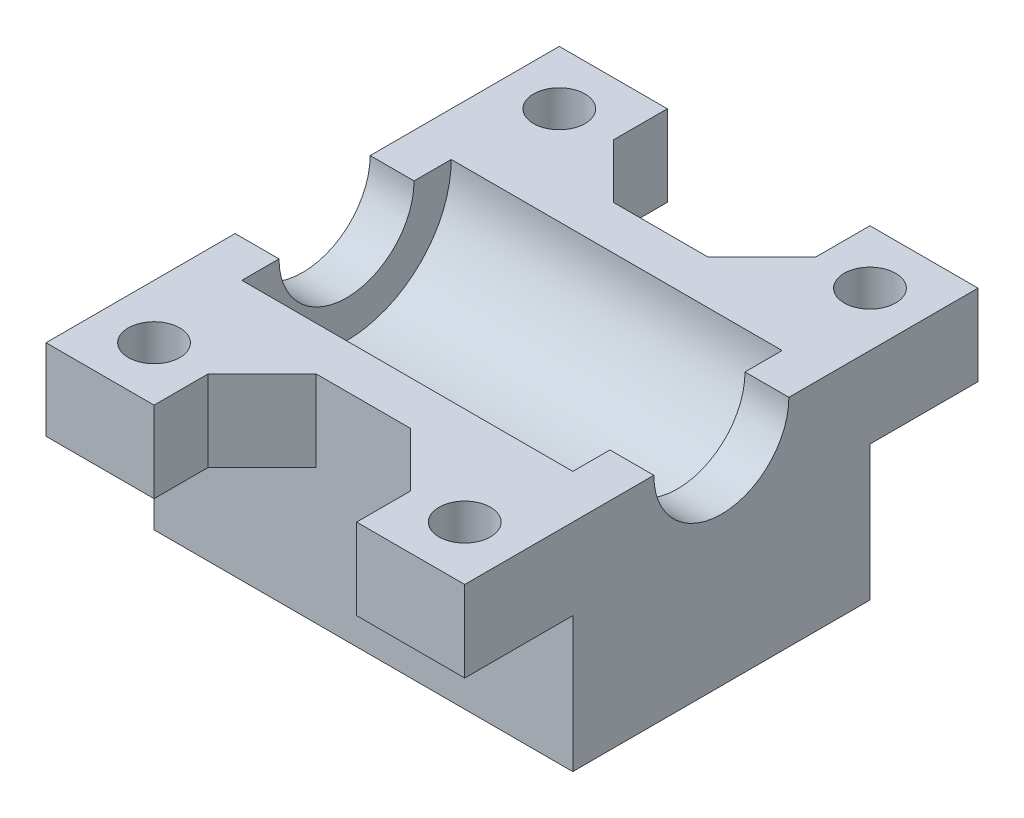
SolidWorks part; units mm, degrees
ref_plane "Front Plane" through (0, 0, 0) normal (0, 0, 1) x (1, 0, 0)
ref_plane "Top Plane" through (0, 0, 0) normal (0, 1, 0) x (1, 0, 0)
ref_plane "Right Plane" through (0, 0, 0) normal (1, 0, 0) x (0, 0, -1)
sketch "Sketch1" plane through (0, 0, 0) normal (0, 1, 0) x (1, 0, 0)
  line L1 (-15.5, 11) -> (15.5, 11)
  line L2 (-15.5, 11) -> (-15.5, -11)
  line L3 (-15.5, -11) -> (15.5, -11)
  line L4 (15.5, 11) -> (15.5, -11)
  line L5 (-15.5, 11) -> (15.5, -11) construction
  line L6 (-15.5, -11) -> (15.5, 11) construction
  point P0 (0, 0)
  dimension "D1" = 31
  dimension "D2" = 22
extrude "Boss-Extrude1" add sketch "Sketch1" along normal blind 11
sketch "Sketch2" plane through (0, 0, 0) normal (0, 1, 0) x (1, 0, 0)
  line L4 (15.5, -11) -> (15.5, 11)
  line L5 (-15.5, -11) -> (15.5, -11)
  line L6 (-15.5, 11) -> (-15.5, -11)
  line L7 (15.5, 11) -> (-15.5, 11)
  line L8 (15.5, -11) -> (15.5, 11)
  line L9 (-15.5, -11) -> (15.5, -11)
  line L10 (-15.5, 11) -> (-15.5, -11)
  line L11 (15.5, 11) -> (-15.5, 11)
  circle A0 centre (0, 0) radius 7.8438
  dimension "D1" = 0
extrude "Boss-Extrude2" add sketch "Sketch2" against normal blind 5
sketch "Sketch3" plane through (0, 11, 0) normal (0, 1, 0) x (1, 0, 0)
  line L1 (12.25, -7.75) -> (-12.25, -7.75)
  line L2 (12.25, -7.75) -> (12.25, 7.75)
  line L3 (12.25, 7.75) -> (-12.25, 7.75)
  line L4 (-12.25, -7.75) -> (-12.25, 7.75)
  line L5 (12.25, -7.75) -> (-12.25, 7.75) construction
  line L6 (12.25, 7.75) -> (-12.25, -7.75) construction
  point P0 (0, 0)
  dimension "D1" = 15.5
  dimension "D2" = 24.5
extrude "Cut-Extrude1" cut sketch "Sketch3" against normal blind 7.75
fillet "Fillet1" radius 7.75 2 edges at (0, 3.25, 7.75) (0, 3.25, -7.75)
sketch "Sketch4" plane through (-12.25, 0, 0) normal (1, 0, 0) x (0, 0, -1)
  line L0 (7.75, 11) -> (-7.75, 11) construction
  circle A0 centre (0, 11) radius 5
  point P4 (0, 0)
  dimension "D1" = 10
extrude "Cut-Extrude2" cut sketch "Sketch4" against normal through all both and the other way through all
sketch "Sketch5" plane through (0, 11, 0) normal (0, 1, 0) x (1, 0, 0)
  line L1 (15.5, -11) -> (7.5, -11)
  line L2 (15.5, -11) -> (15.5, -19)
  line L3 (15.5, -19) -> (7.5, -19)
  line L4 (7.5, -11) -> (7.5, -19)
  circle A0 centre (11.5, -15) radius 1.9058
  dimension "D1" = 8
  dimension "D2" = 8
  dimension "D3" = 4
  dimension "D4" = 4
extrude "Boss-Extrude3" add sketch "Sketch5" against normal blind 6
sketch "Sketch6" plane through (0, 5, 0) normal (0, -1, 0) x (1, 0, 0)
  line L4 (15.5, 11) -> (15.5, 19)
  line L5 (15.5, 19) -> (7.5, 19)
  line L6 (7.5, 19) -> (7.5, 11)
  line L7 (7.5, 11) -> (15.5, 11)
  line L8 (15.5, 11) -> (15.5, 19)
  line L9 (15.5, 19) -> (7.5, 19)
  line L10 (7.5, 19) -> (7.5, 11)
  line L11 (7.5, 11) -> (15.5, 11)
  circle A0 centre (11.5, 15) radius 1.9058 construction
  circle A1 centre (11.5, 15) radius 1.9058
  circle A2 centre (11.5, 15) radius 3
  circle M6 centre (11.5, 15) radius 1.9058
  dimension "D2" = 6
  dimension "D1" = 0
extrude "Cut-Extrude3" cut sketch "Sketch6" against normal blind 3 contours A2 M6 region at (8.5849, 5, 15)
mirror "Mirror8" about plane through (0, 0, 0) normal (1, 0, 0) of "Cut-Extrude3", "Boss-Extrude3"
mirror "Mirror9" about plane through (0, 0, 0) normal (0, 0, 1) of "Mirror8"
chamfer "Chamfer2" distance 4 angle 45 4 edges at (-7.5, 8, 11) (7.5, 8, 11) (-7.5, 8, -11) (7.5, 8, -11)
